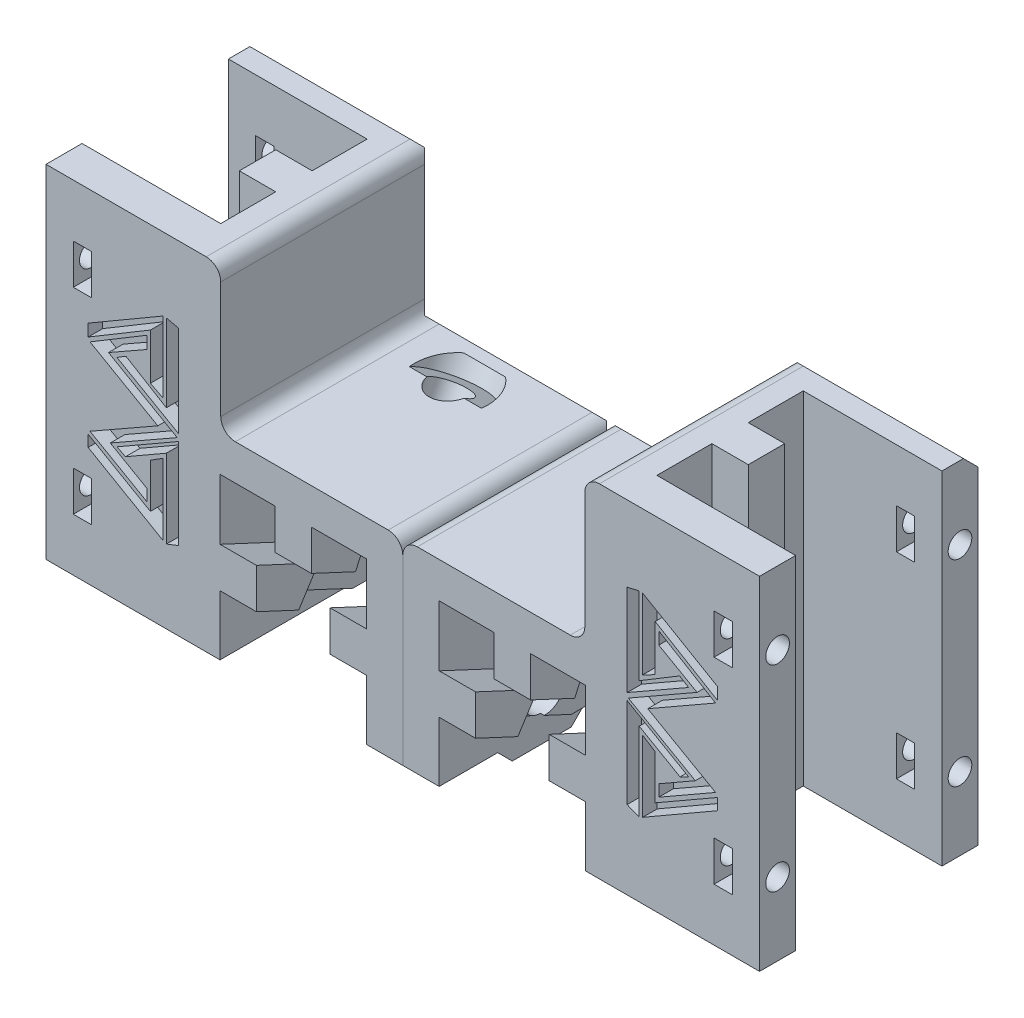
SolidWorks part; units mm, degrees
ref_plane "Front Plane" through (0, 0, 0) normal (0, 0, 1) x (1, 0, 0)
ref_plane "Top Plane" through (0, 0, 0) normal (0, 1, 0) x (1, 0, 0)
ref_plane "Right Plane" through (0, 0, 0) normal (1, 0, 0) x (0, 0, -1)
sketch "Sketch1" plane through (0, 0, 0) normal (0, 1, 0) x (1, 0, 0)
  line L1 (-15, -15) -> (15, -15)
  line L2 (-15, -15) -> (-15, 15)
  line L3 (-15, 15) -> (15, 15)
  line L4 (15, -15) -> (15, 15)
  line L5 (-15, -15) -> (15, 15) construction
  line L6 (-15, 15) -> (15, -15) construction
  point P0 (0, 0)
  dimension "D1" = 30
  dimension "D2" = 30
extrude "Boss-Extrude1" add sketch "Sketch1" along normal blind 50
sketch "Sketch2" plane through (0, 50, 0) normal (0, 1, 0) x (1, 0, 0)
  line L1 (-10.05, -10.05) -> (10.05, -10.05)
  line L2 (-10.05, -10.05) -> (-10.05, 10.05)
  line L3 (-10.05, 10.05) -> (10.05, 10.05)
  line L4 (10.05, -10.05) -> (10.05, 10.05)
  line L5 (-10.05, -10.05) -> (10.05, 10.05) construction
  line L6 (-10.05, 10.05) -> (10.05, -10.05) construction
  line L7 (-10.05, 0) -> (10.05, 0) construction
  line L8 (-10.05, 2.5) -> (-5.05, 2.5)
  line L9 (-5.05, 2.5) -> (-5.05, -2.5)
  line L10 (-5.05, -2.5) -> (-10.05, -2.5)
  point P0 (0, 0)
  dimension "D1" = 20.1
  dimension "D2" = 20.1
  dimension "D3" = 5
  dimension "D4" = 2.5
  dimension "D5" = 5
extrude "Cut-Extrude1" cut sketch "Sketch2" against normal through all contours L9 L10 L2 L1 L4 L3 L8 region at (0.498, 50, 0)
sketch "Sketch3" plane through (0, 50, 0) normal (0, 1, 0) x (1, 0, 0)
  line L0 (15, 15) -> (-15, 15) construction
  line L1 (9, 15) -> (15, 15)
  line L2 (9, 15) -> (9, -15)
  line L3 (9, -15) -> (15, -15)
  line L4 (15, 15) -> (15, -15)
  line L5 (-15, -15) -> (15, -15) construction
  dimension "D1" = 6
extrude "Cut-Extrude2" cut sketch "Sketch3" against normal through all
sketch "Sketch5" plane through (-15, 0, 0) normal (-1, 0, 0) x (0, 0, 1)
  line L1 (-15, 30) -> (15, 30)
  line L2 (-15, 30) -> (-15, 0)
  line L3 (-15, 0) -> (15, 0)
  line L4 (15, 30) -> (15, 0)
extrude "Boss-Extrude2" add sketch "Sketch5" along normal blind 25
sketch "Sketch6" plane through (-40, 0, 0) normal (-1, 0, 0) x (0, 0, 1)
  line L0 (-23.4514, 12.0698) -> (15, 30) construction
  line L1 (15, 0) -> (15, 30) construction
  dimension "D1" = 65
ref_plane "45 Angle plane" through (-40, 12.0698, -23.4514) normal (0, -0.4226, -0.9063) x (-1, 0, 0)
sketch "Sketch7" plane through (-40, 12.0698, -23.4514) normal (0, -0.4226, -0.9063) x (-1, 0, 0)
  line L0 (-49, -14.5107) -> (0, -14.5107) construction
  line L1 (-25.1, -24.5607) -> (-5, -24.5607)
  line L2 (-25.1, -24.5607) -> (-25.1, -4.4607)
  line L3 (-25.1, -4.4607) -> (-5, -4.4607)
  line L4 (-5, -24.5607) -> (-5, -4.4607)
  line L5 (-25.1, -24.5607) -> (-5, -4.4607) construction
  line L6 (-25.1, -4.4607) -> (-5, -24.5607) construction
  line L7 (0, -14.5107) -> (0, -27.1892) construction
  line L8 (-15.05, -4.4607) -> (-15.05, -24.5607) construction
  line L9 (-25.1, -14.5107) -> (-5, -14.5107)
  line L10 (-12.55, -4.4607) -> (-12.55, -9.4607)
  line L11 (-12.55, -9.4607) -> (-17.55, -9.4607)
  line L12 (-17.55, -9.4607) -> (-17.55, -4.4607)
  line L13 (-25.1, -12.0107) -> (-20.1, -12.0107)
  line L14 (-20.1, -12.0107) -> (-20.1, -17.0107)
  line L15 (-20.1, -17.0107) -> (-25.1, -17.0107)
  line L16 (-12.55, -24.5607) -> (-12.55, -19.5607)
  line L17 (-12.55, -19.5607) -> (-17.55, -19.5607)
  line L18 (-17.55, -19.5607) -> (-17.55, -24.5607)
  line L19 (-5, -12.0107) -> (-10, -12.0107)
  line L20 (-10, -12.0107) -> (-10, -17.0107)
  line L21 (-10, -17.0107) -> (-5, -17.0107)
  point P0 (-15.05, -14.5107)
  dimension "D1" = 20.1
  dimension "D2" = 20.1
  dimension "D3" = 5
  dimension "D4" = 5
  dimension "D5" = 2.5
  dimension "D6" = 5
  dimension "D7" = 5
  dimension "D8" = 5
  dimension "D9" = 2.5
extrude "45 degree extrusion cut" cut sketch "Sketch7" against normal through all contours L21 L20 L9 L14 L15 L2 L1 L18 L17 L16 L4 | L20 L19 L4 L3 L10 L11 L12 L2 L13 L14 L9 region at (-15.1247, -6.7684, -14.667) region at (-15.1247, 4.6058, -19.9708)
sketch "Sketch11" plane through (9, 0, 0) normal (1, 0, 0) x (0, 0, -1)
  line L0 (12.525, 50) -> (12.525, 40) construction
  line L1 (15, 50) -> (10.05, 50) construction
  line L2 (12.525, 0) -> (12.525, 13) construction
  line L3 (15, 0) -> (10.05, 0) construction
  line L4 (-12.525, 0) -> (-12.525, 13) construction
  line L5 (-10.05, 0) -> (-15, 0) construction
  line L6 (-12.525, 50) -> (-12.525, 40) construction
  line L7 (-10.05, 50) -> (-15, 50) construction
  circle A0 centre (-12.525, 40) radius 1.625
  circle A1 centre (12.525, 40) radius 1.625
  circle A2 centre (12.525, 13) radius 1.625
  circle A3 centre (-12.525, 13) radius 1.625
  dimension "D5" = 3.25
  dimension "D6" = 3.25
  dimension "D7" = 3.25
  dimension "D8" = 3.25
  dimension "D1" = 10
  dimension "D2" = 10
  dimension "D3" = 13
  dimension "D4" = 13
extrude "Cut-Extrude7" cut sketch "Sketch11" against normal blind 10
chamfer "Chamfer1" distance 2 angle 45 6 edges at (-5.45, 0, -15) (-35, 0, -15) (-3, 50, -15) (-40, 15, -15)
fillet "Fillet1" radius 2 4 edges at (-15, 50, 1) (-40, 30, 1) (-40, 0, 1)
sketch "Sketch16" plane through (-40, 0, 0) normal (-1, 0, 0) x (0, 0, 1)
  line L0 (15, 13.9434) -> (-13, 0.8868) construction
  line L1 (15, 2) -> (15, 28) construction
  line L2 (-13, 28) -> (-13, 2) construction
  line L3 (-23.4514, 12.0698) -> (15, 30) construction
  circle A0 centre (1, 7.4151) radius 2.675
  dimension "D1" = 5.35
extrude "Cut-Extrude10" cut sketch "Sketch16" against normal blind 10
ref_plane "Plane1" through (-25, 0, 0) normal (-1, 0, 0) x (0, 0, 1)
sketch "Sketch18" plane through (-25, 0, 0) normal (-1, 0, 0) x (0, 0, 1)
  line L0 (14.8471, 13.729) -> (1, 7.4151) construction
  line L4 (9.9507, 7.3478) -> (5.6064, 14.1277)
  line L5 (9.9507, 7.3478) -> (-3.6064, 0.7025)
  line L6 (5.6064, 14.1277) -> (-7.9507, 7.4825)
  line L7 (-3.6064, 0.7025) -> (-7.9507, 7.4825)
  dimension "D1" = 8
  dimension "D2" = 15
  dimension "D3" = 7.5
  dimension "D4" = 4
extrude "Cut-Extrude11" cut sketch "Sketch18" against normal mid plane 19
fillet "Fillet2" radius 0.5 1 edges at (-24.95, 0, -3.0507)
fillet "Fillet3" radius 0.5 1 edges at (-24.95, 8.4172, 15)
sketch "Sketch19" plane through (0, 0, 15) normal (0, 0, 1) x (1, 0, 0)
  line L0 (-40, 2) -> (-40, 28) construction
  line L1 (-40, 3) -> (9, 3)
  line L2 (-40, 3) -> (-40, 0)
  line L3 (-40, 0) -> (9, 0)
  line L4 (9, 3) -> (9, 0)
  dimension "D1" = 3
extrude "Cut-Extrude12" cut sketch "Sketch19" against normal through all
sketch "Sketch20" plane through (0, 0, 15) normal (0, 0, 1) x (1, 0, 0)
  line L1 (-28.5785, 8.4284) -> (-21.8248, 8.4284)
  line L2 (-28.5785, 8.4284) -> (-28.5785, 2.1753)
  line L3 (-28.5785, 2.1753) -> (-21.8248, 2.1753)
  line L4 (-21.8248, 8.4284) -> (-21.8248, 2.1753)
extrude "Cut-Extrude13" cut sketch "Sketch20" against normal blind 15
sketch "Sketch21" plane through (-25, 0, 0) normal (-1, 0, 0) x (0, 0, 1)
  line L0 (-7.6246, 31.9083) -> (1.6243, 14.3185) construction
ref_plane "Plane2" through (-25, 31.9083, -7.6246) normal (0, 0.8851, -0.4654) x (1, 0, 0)
sketch "Sketch22" plane through (-25, 31.9083, -7.6246) normal (0, 0.8851, -0.4654) x (1, 0, 0)
  circle A0 centre (0.022, 0.0143) radius 2.65
  dimension "D1" = 5.3
extrude "Cut-Extrude14" cut sketch "Sketch22" against normal through all
sketch "Sketch23" plane through (-25, 31.9083, -7.6246) normal (0, 0.8851, -0.4654) x (1, 0, 0)
  circle A0 centre (0.022, 0.0143) radius 5
  dimension "D1" = 10
extrude "Cut-Extrude15" cut sketch "Sketch23" against normal blind 2.5
sketch "Sketch24" plane through (0, 10.3222, -4.8133) normal (0, -0.9063, 0.4226) x (1, 0, 0)
  line L0 (-27.45, 21.8616) -> (-27.45, 8.5079) construction
  line L1 (-27.45, 15.1847) -> (-22.45, 15.1847)
  line L2 (-27.45, 15.1847) -> (-27.45, 0.1847)
  line L3 (-27.45, 0.1847) -> (-22.45, 0.1847)
  line L4 (-22.45, 15.1847) -> (-22.45, 0.1847)
  line L5 (-22.45, 6.7563) -> (-22.45, -11.2398) construction
  dimension "D1" = 15
extrude "Cut-Extrude16" cut sketch "Sketch24" against normal blind 4
sketch "Sketch25" plane through (0, 3, 0) normal (0, -1, 0) x (1, 0, 0)
  line L0 (-40, -23.4514) -> (-40, 15) construction
  line L1 (-40, 6.9649) -> (-35, 6.9649)
  line L2 (-40, 6.9649) -> (-40, -5.1295)
  line L3 (-40, -5.1295) -> (-35, -5.1295)
  line L4 (-35, 6.9649) -> (-35, -5.1295)
  line L5 (-35, 15) -> (-35, -2.651) construction
extrude "Boss-Extrude3" add sketch "Sketch25" along normal blind 2
chamfer "Chamfer2" distance 2 angle 45 2 edges at (-37.5, 1, -5.1295) (-37.5, 1, 6.9649)
sketch "Sketch26" plane through (0, 0, 15) normal (0, 0, 1) x (1, 0, 0)
  line L0 (4, 50) -> (4, 40) construction
  line L1 (-13, 50) -> (9, 50) construction
  line L2 (4, 3) -> (4, 13) construction
  line L3 (9, 3) -> (-14.9, 3) construction
  line L4 (9, 3) -> (9, 50) construction
  line L6 (2.75, 37.25) -> (5.25, 37.25)
  line L7 (2.75, 37.25) -> (2.75, 42.75)
  line L8 (2.75, 42.75) -> (5.25, 42.75)
  line L9 (5.25, 37.25) -> (5.25, 42.75)
  line L10 (2.75, 37.25) -> (5.25, 42.75) construction
  line L11 (2.75, 42.75) -> (5.25, 37.25) construction
  line L12 (2.75, 10.25) -> (5.25, 10.25)
  line L13 (2.75, 10.25) -> (2.75, 15.75)
  line L14 (2.75, 15.75) -> (5.25, 15.75)
  line L15 (5.25, 10.25) -> (5.25, 15.75)
  line L16 (2.75, 10.25) -> (5.25, 15.75) construction
  line L17 (2.75, 15.75) -> (5.25, 10.25) construction
  dimension "D1" = 10
  dimension "D2" = 5
  dimension "D3" = 10
  dimension "D4" = 5
  dimension "D5" = 5.5
  dimension "D6" = 2.5
  dimension "D7" = 2.5
  dimension "D8" = 5.5
extrude "Cut-Extrude17" cut sketch "Sketch26" against normal through all
fillet "Fillet4" radius 0.5 3 edges at (-24.95, 5.5721, -15) (-32.5, 3, -14.482) (-17.4, 3, -14.482)
sketch "Mobious Logo" plane through (0, 0, 15) normal (0, 0, 1) x (-1, 0, 0)
  line L0 (-3.2109, -32.3487) -> (-3.2109, -34.0037)
  line L1 (-3.2109, -34.0037) -> (7.0562, -39.9788)
  line L2 (7.0562, -39.9788) -> (7.0562, -30.2448)
  line L3 (7.0562, -30.2448) -> (5.3383, -31.1222)
  line L4 (5.3383, -31.1222) -> (5.3383, -37.4541)
  line L5 (5.3383, -37.4541) -> (-3.2109, -32.3487)
  line L6 (1.9787, -32.6572) -> (0.7445, -31.8998)
  line L7 (0.7445, -31.8998) -> (9.1881, -27.0749)
  line L8 (9.1881, -27.0749) -> (9.1881, -39.6141)
  line L9 (9.1881, -39.6141) -> (7.533, -39.9851)
  line L10 (7.533, -39.9851) -> (7.533, -29.3079)
  line L11 (7.533, -29.3079) -> (1.9787, -32.6572)
  line L12 (4.84, -36.5845) -> (-2.9584, -31.8998)
  line L13 (-2.9584, -31.8998) -> (6.3555, -26.5699)
  line L14 (6.3555, -26.5699) -> (-2.9584, -21.2681)
  line L15 (-2.9584, -21.2681) -> (4.84, -16.8055)
  line L16 (4.84, -16.8055) -> (4.84, -18.4002)
  line L17 (4.84, -18.4002) -> (-0.1715, -21.2681)
  line L18 (-0.1715, -21.2681) -> (9.0195, -26.5)
  line L19 (9.0195, -26.5) -> (-0.4166, -31.8998)
  line L20 (-0.4166, -31.8998) -> (4.84, -34.8921)
  line L21 (4.84, -34.8921) -> (4.84, -36.5845)
  line L22 (-3.2109, -20.7912) -> (-3.2109, -19.2203)
  line L23 (-3.2109, -19.2203) -> (7.0562, -13.3014)
  line L24 (7.0562, -13.3014) -> (7.0562, -23.0634)
  line L25 (7.0562, -23.0634) -> (5.3383, -21.9694)
  line L26 (5.3383, -21.9694) -> (5.3383, -15.8821)
  line L27 (5.3383, -15.8821) -> (-3.2109, -20.7912)
  line L28 (0.7445, -21.2681) -> (9.1881, -26.1211)
  line L29 (9.1881, -26.1211) -> (9.1881, -13.7502)
  line L30 (9.1881, -13.7502) -> (7.533, -13.0939)
  line L31 (7.533, -13.0939) -> (7.533, -23.905)
  line L32 (7.533, -23.905) -> (1.9157, -20.6765)
  line L33 (1.9157, -20.6765) -> (0.7445, -21.2681)
  line L34 (-9, -26.5) -> (14.8874, -26.5) construction
  line L35 (-9, -3) -> (-9, -50) construction
extrude "Cut-Extrude18" cut sketch "Mobious Logo" against normal blind 2
mirror "Mirror1" about plane through (-40, 0, 0) normal (-1, 0, 0) of bodies 121
